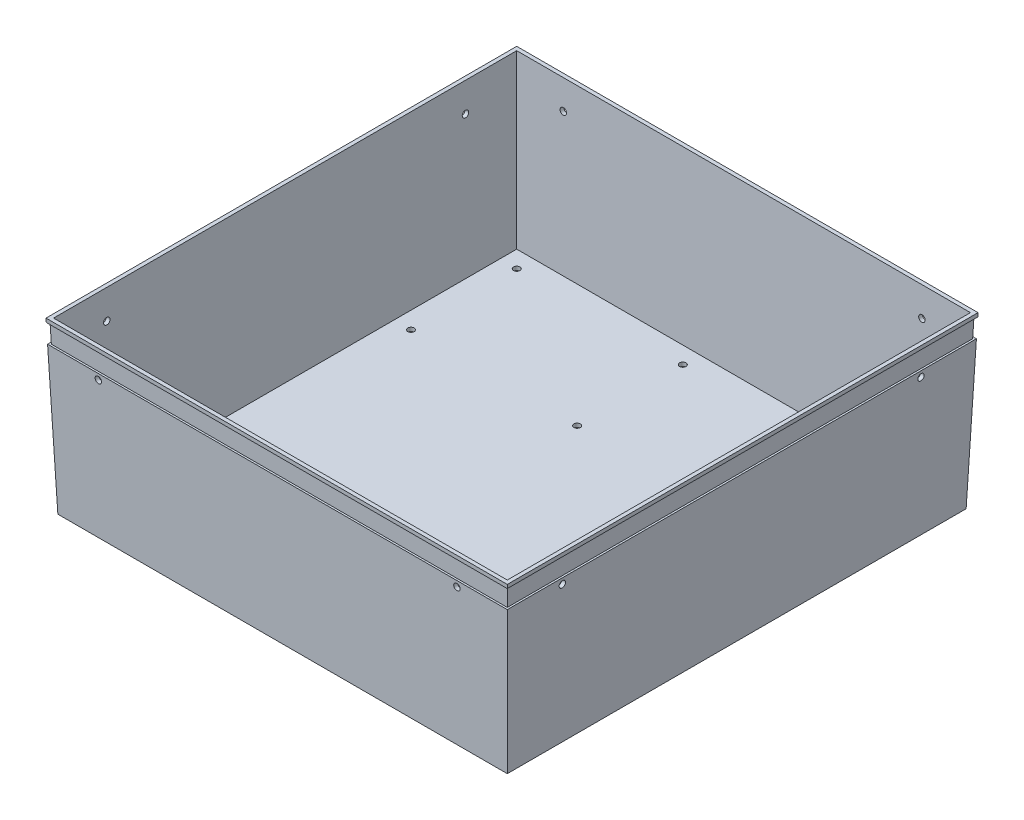
SolidWorks part; units mm, degrees
note: '?' marks a value the reader was unsure of.
ref_plane "Front Plane" through (0, 0, 0) normal (0, 0, 1) x (1, 0, 0)
ref_plane "Top Plane" through (0, 0, 0) normal (0, 1, 0) x (1, 0, 0)
ref_plane "Right Plane" through (0, 0, 0) normal (1, 0, 0) x (0, 0, -1)
sketch "Sketch1" plane through (0, 0, 0) normal (0, 1, 0) x (1, 0, 0)
  line L1 (-119.05, -121.55) -> (119.05, -121.55)
  line L2 (-119.05, -121.55) -> (-119.05, 121.55)
  line L3 (-119.05, 121.55) -> (119.05, 121.55)
  line L4 (119.05, -121.55) -> (119.05, 121.55)
  line L5 (-119.05, -121.55) -> (119.05, 121.55) construction
  line L6 (-119.05, 121.55) -> (119.05, -121.55) construction
  point P0 (0, 0)
  dimension "D1" = 243.1
  dimension "D2" = 238.1
extrude "Boss-Extrude1" add sketch "Sketch1" along normal blind 90 draft 2 draft outward yes
shell "Shell1" thickness 2
sketch "Sketch6" plane through (0, -4.2394, 121.402) normal (0, -0.0349, 0.9994) x (1, 0, 0)
  line L0 (-122.1231, 92.2969) -> (-121.7743, 82.303)
  line L1 (-122.1929, 94.2969) -> (-119.05, 4.242) construction
  line L2 (-121.7743, 82.303) -> (-120.7737, 82.303)
  line L3 (-120.7737, 82.303) -> (-121.1225, 92.2969)
  line L4 (-121.1225, 92.2969) -> (-122.1231, 92.2969)
  line L5 (-122.1929, 94.2969) -> (122.1929, 94.2969) construction
  line L6 (122.1929, 94.2969) -> (119.05, 4.242) construction
  point P8 (-121.9487, 87.2999)
  point P9 (121.9487, 87.2999)
  dimension "D1" = 2
  dimension "D2" = 10
  dimension "D3" = 1
sketch "Sketch7" plane through (-118.905, -4.1523, 0) normal (-0.9994, -0.0349, 0) x (0, 0, 1)
  line L0 (124.6243, 92.2096) -> (123.6243, 92.2096)
  line L1 (124.2743, 82.1808) -> (124.6231, 92.1747) construction
  line L2 (123.6243, 92.2096) -> (123.2755, 82.2157)
  line L3 (123.2755, 82.2157) -> (124.2755, 82.2157)
  line L4 (124.6243, 92.2096) -> (124.2755, 82.2157)
  line L5 (-124.6929, 94.2096) -> (124.6929, 94.2096) construction
  line L6 (-124.6929, 94.2096) -> (-121.55, 4.1548) construction
  point P8 (124.4487, 87.2127)
  point P9 (-124.4487, 87.2127)
  point P11 (0, 0)
  dimension "D1" = 1
  dimension "D2" = 10
  dimension "D3" = 2
ref_axis "Axis5" through (-121.9487, 83.0073, 124.4487) along (1, 0, 0)?
ref_axis "Axis6" through (-121.9487, 83.0073, 124.4487) along (0, 0, -1)?
extrude "Cut-Extrude7" cut sketch "Sketch6" along direction (0, 0, -1) on the side against the normal through all
extrude "Cut-Extrude8" cut sketch "Sketch7" along direction (1, 0, 0) on the side against the normal through all
mirror "Mirror1" about plane through (0, 0, 0) normal (1, 0, 0) of "Cut-Extrude7"
mirror "Mirror2" about plane through (0, 0, 0) normal (0, 0, 1) of "Cut-Extrude8"
sketch "Sketch10" plane through (0, -4.2394, 121.402) normal (0, -0.0349, 0.9994) x (1, 0, 0)
  line L0 (-122.1929, 94.2969) -> (122.1929, 94.2969) construction
  line L1 (0, -49.5) -> (0, 49.5) construction
  line L5 (-120.1917, 94.2271) -> (120.1917, 94.2271) construction
  circle A0 centre (-95, 79.2271) radius 1.7
  circle A1 centre (95, 79.2271) radius 1.7
  point P4 (0, 94.2969)
  dimension "D3" = 3.4
  dimension "D1" = 15
  dimension "D2" = 95
extrude "Cut-Extrude11" cut sketch "Sketch10" against normal blind 3
mirror "Mirror3" about plane through (0, 0, 0) normal (0, 0, 1) of "Cut-Extrude11"
sketch "Sketch11" plane through (-118.905, -4.1523, 0) normal (-0.9994, -0.0349, 0) x (0, 0, 1)
  line L3 (0, -12.792) -> (0, 26.9102) construction
  line L4 (-122.6917, 94.1398) -> (122.6917, 94.1398) construction
  circle A0 centre (-95, 79.1398) radius 1.7
  circle A2 centre (95, 79.1398) radius 1.7
  dimension "D2" = 3.4
  dimension "D3" = 15
  dimension "D1" = 95
extrude "Cut-Extrude12" cut sketch "Sketch11" against normal blind 3
mirror "Mirror4" about plane through (0, 0, 0) normal (1, 0, 0) of "Cut-Extrude12"
sketch "Sketch12" plane through (0, 2, 0) normal (0, 1, 0) x (1, 0, 0)
  line L0 (-108.1186, 47.6186) -> (-20.1186, 47.6186) construction
  line L1 (-115.1186, 54.6186) -> (-115.1186, 110.6186) construction
  line L2 (-108.1186, 117.6186) -> (-20.1186, 117.6186) construction
  line L3 (-13.1186, 54.6186) -> (-13.1186, 110.6186) construction
  line L4 (-115.1186, 47.6186) -> (-13.1186, 117.6186) construction
  line L5 (-115.1186, 117.6186) -> (-13.1186, 47.6186) construction
  line L6 (-117.1186, 119.6186) -> (-117.1186, -119.6186) construction
  line L7 (117.1186, 119.6186) -> (-117.1186, 119.6186) construction
  arc A0 (-20.1186, 117.6186) -> (-13.1186, 110.6186) centre (-20.1186, 110.6186) cw construction
  arc A1 (-20.1186, 47.6186) -> (-13.1186, 54.6186) centre (-20.1186, 54.6186) ccw construction
  arc A2 (-108.1186, 47.6186) -> (-115.1186, 54.6186) centre (-108.1186, 54.6186) cw construction
  arc A3 (-115.1186, 110.6186) -> (-108.1186, 117.6186) centre (-108.1186, 110.6186) cw construction
  circle A4 centre (-108.1186, 110.6186) radius 4 construction
  circle A5 centre (-20.1186, 110.6186) radius 4 construction
  circle A6 centre (-108.1186, 54.6186) radius 4 construction
  circle A7 centre (-20.1186, 54.6186) radius 4 construction
  point P0 (-64.1186, 82.6186)
  point P21 (-108.1186, 110.6186)
  point P22 (-20.1186, 110.6186)
  point P23 (-20.1186, 54.6186)
  point P24 (-108.1186, 54.6186)
  point P25 (-108.1186, 110.6186)
  point P26 (-20.1186, 110.6186)
  point P27 (-20.1186, 54.6186)
  point P28 (-108.1186, 54.6186)
  dimension "D3" = 7
  dimension "D4" = 8
  dimension "D1" = 102
  dimension "D2" = 70
  dimension "D5" = 2
  dimension "D6" = 2
hole_wizard "M3 Clearance Hole2" positions "Sketch12" profile "Sketch14" hole size "M3" standard "ISO"
sketch "Sketch14" plane through (-108.1186, 2, -54.6186) normal (1, 0, 0) x (0, 0, 1)
  line L0 (0, 0) -> (0, 2)
  line L1 (0, 2) -> (1.7, 2)
  line L2 (1.7, 2) -> (1.7, 0)
  line L5 (1.7, 0) -> (0, 0)
  line L11 (0, -6.35) -> (0, 107.95) construction
  dimension "Thru Hole Dia." = 3.4
  dimension "Thru Hole Depth" = 2
